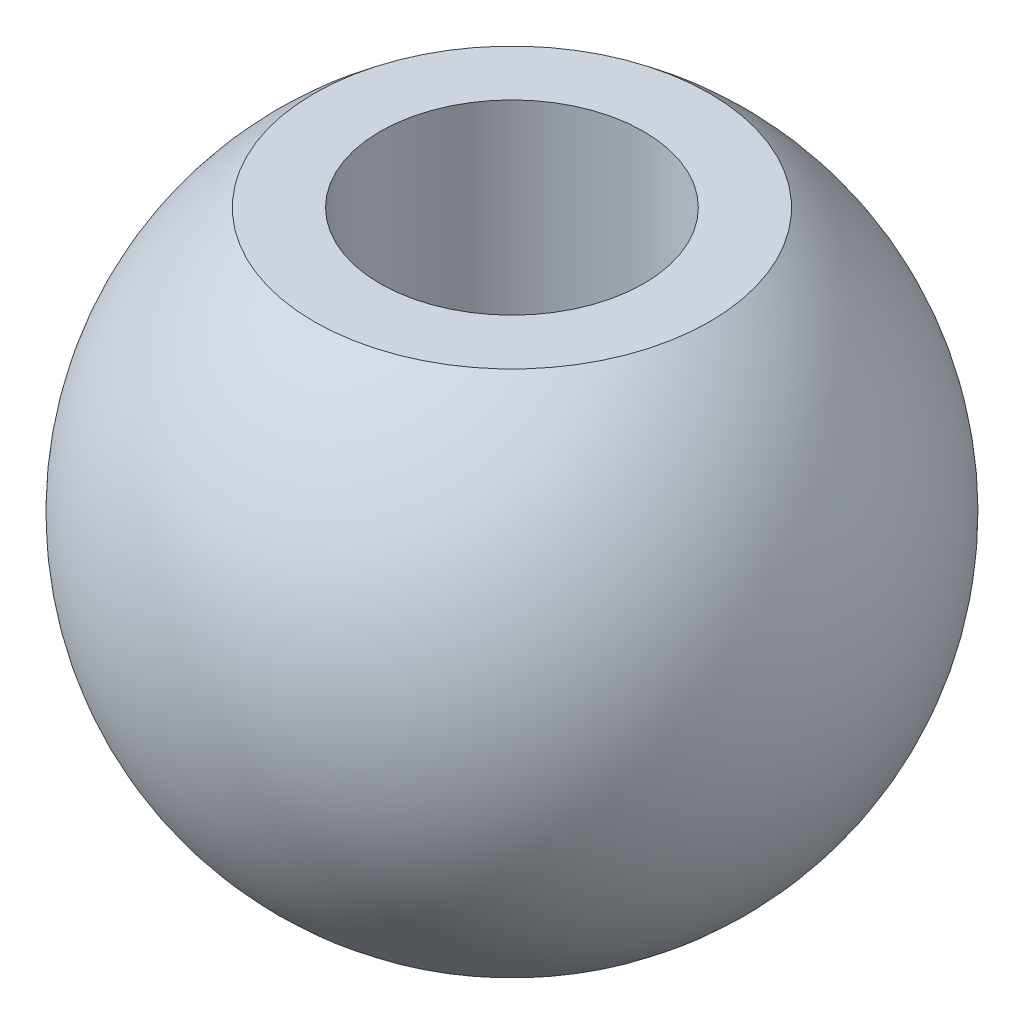
SolidWorks part; units mm, degrees
ref_plane "Front Plane" through (0, 0, 0) normal (0, 0, 1) x (1, 0, 0)
ref_plane "Top Plane" through (0, 0, 0) normal (0, 1, 0) x (1, 0, 0)
ref_plane "Right Plane" through (0, 0, 0) normal (1, 0, 0) x (0, 0, -1)
sketch "Sketch1" plane through (0, 0, 0) normal (0, 1, 0) x (1, 0, 0)
  line L0 (0, 2.5) -> (0, -2.5)
  arc A0 (0, -2.5) -> (0, 2.5) centre (0, 0) ccw
  dimension "D1" = 5
revolve "Revolve1" add sketch "Sketch1" angle 360 about L0
sketch "Sketch2" plane through (0, 0, 0) normal (0, 0, 1) x (1, 0, 0)
  line L0 (-2.75, 0) -> (2.7143, 0) construction
  line L1 (0, 2) -> (0, -2)
  line L3 (-1.5, -2) -> (1.5017, -2)
  line L4 (-1.5, -2) -> (-1.5, -2.8645)
  line L5 (-1.5, -2.8645) -> (1.5017, -2.8645)
  line L6 (1.5017, -2) -> (1.5017, -2.8645)
  line L7 (-1.5, 2) -> (1.5017, 2)
  line L8 (-1.5, 2) -> (-1.5, 2.9006)
  line L9 (-1.5, 2.9006) -> (1.5017, 2.9006)
  line L10 (1.5017, 2) -> (1.5017, 2.9006)
  circle A0 centre (0, 0) radius 2.5 construction
  point P6 (0, 0)
  dimension "D1" = 4
extrude "Cut-Extrude1" cut sketch "Sketch2" against normal blind 10 and the other way blind 10 contours L7 L10 L9 L8 | L6 L3 L4 L5 region at (0.0008, -2.4322, 0) region at (0.0008, 2.4503, 0)
sketch "Sketch3" plane through (0, -2, 0) normal (0, -1, 0) x (1, 0, 0)
  circle A0 centre (0, 0) radius 1
  dimension "D1" = 2
extrude "Cut-Extrude2" cut sketch "Sketch3" against normal blind 10
